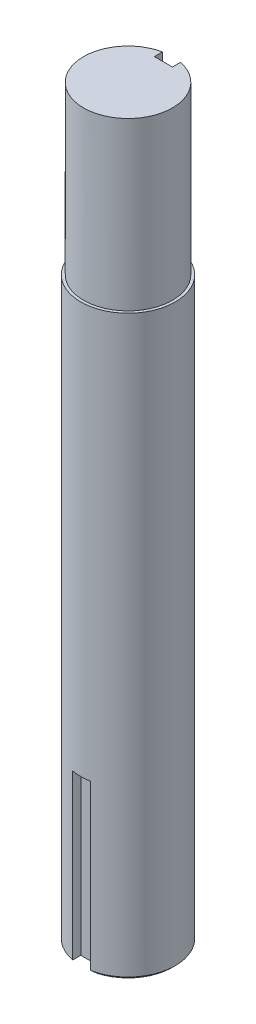
SolidWorks part; units mm, degrees
ref_plane "Front Plane" through (0, 0, 0) normal (0, 0, 1) x (1, 0, 0)
ref_plane "Top Plane" through (0, 0, 0) normal (0, 1, 0) x (1, 0, 0)
ref_plane "Right Plane" through (0, 0, 0) normal (1, 0, 0) x (0, 0, -1)
sketch "Sketch1" plane through (0, 0, 0) normal (0, 0, 1) x (1, 0, 0)
  line L5 (8.5, 134) -> (0, 134)
  line L6 (8.5, 134) -> (8.5, 0)
  line L7 (8.5, 0) -> (0, 0)
  line L8 (0, 134) -> (0, 0)
  line L9 (8.5, 134) -> (0, 0) construction
  line L10 (8.5, 0) -> (0, 134) construction
  point P0 (4.25, 67)
  dimension "D1" = 8.5
  dimension "D2" = 134
revolve "Revolve1" add sketch "Sketch1" angle 360 about L8
sketch "Sketch2" plane through (0, 0, 0) normal (0, -1, 0) x (1, 0, 0)
  line L1 (-1.625, 10.125) -> (1.625, 10.125)
  line L2 (-1.625, 10.125) -> (-1.625, 6.875)
  line L3 (-1.625, 6.875) -> (1.625, 6.875)
  line L4 (1.625, 10.125) -> (1.625, 6.875)
  line L5 (-1.625, 10.125) -> (1.625, 6.875) construction
  line L6 (-1.625, 6.875) -> (1.625, 10.125) construction
  circle A0 centre (0, 0) radius 8.5 construction
  point P0 (0, 8.5)
  dimension "D1" = 3.25
extrude "Cut-Extrude1" cut sketch "Sketch2" against normal blind 30
ref_axis "Axis1" through (0, 0, 0) along (0, 1, 0)
chamfer "Chamfer1" distance 0.5 angle 45 5 edges at (0, 134, 8.5) (-1.625, 0, 7.6091) (0, 0, 6.875) (1.625, 0, 7.6091) (0, 0, -8.5)
sketch "Sketch4" plane through (0, 134, 0) normal (0, 1, 0) x (1, 0, 0)
  circle A0 centre (0, 0) radius 8
  dimension "D1" = 16
extrude "Cut-Extrude3" cut sketch "Sketch4" against normal blind 30 flip side to cut
sketch "Sketch3" plane through (0, 134, 0) normal (0, 1, 0) x (1, 0, 0)
  line L1 (-1.625, 9.625) -> (1.625, 9.625)
  line L2 (-1.625, 9.625) -> (-1.625, 6.375)
  line L3 (-1.625, 6.375) -> (1.625, 6.375)
  line L4 (1.625, 9.625) -> (1.625, 6.375)
  line L5 (-1.625, 9.625) -> (1.625, 6.375) construction
  line L6 (-1.625, 6.375) -> (1.625, 9.625) construction
  circle A1 centre (0, 0) radius 8 construction
  point P0 (0, 8)
  dimension "D1" = 3.25
extrude "Cut-Extrude2" cut sketch "Sketch3" against normal blind 25
